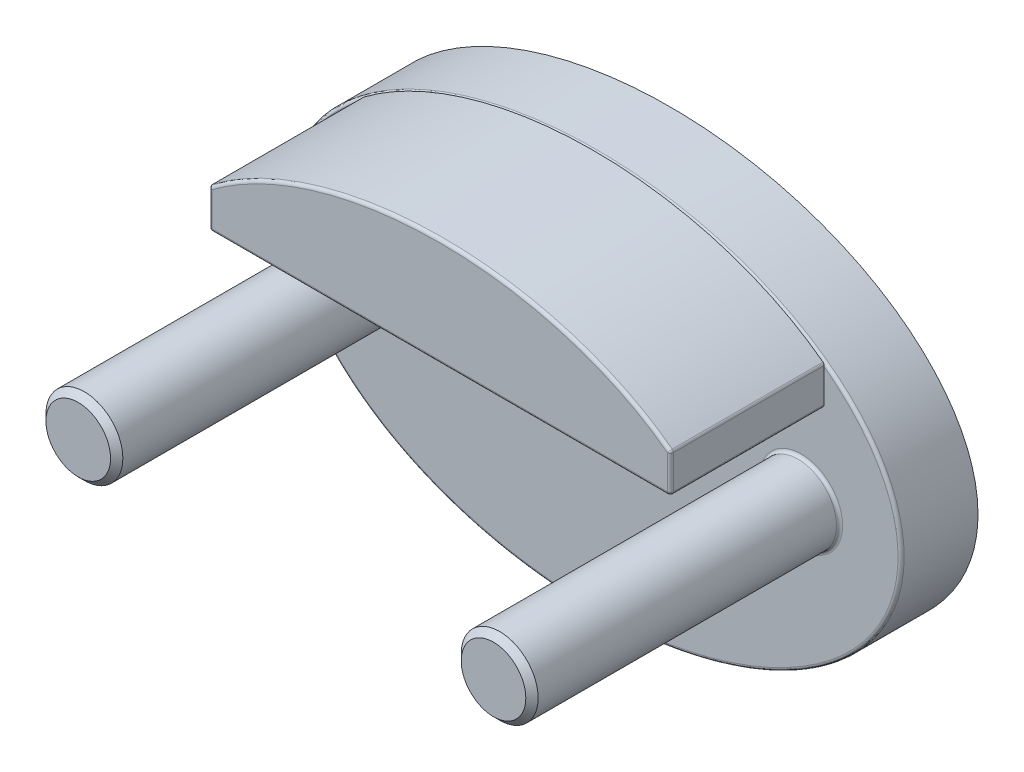
SolidWorks part; units mm, degrees
ref_plane "Face" through (0, 0, 0) normal (0, 0, 1) x (1, 0, 0)
ref_plane "Dessus" through (0, 0, 0) normal (0, 1, 0) x (1, 0, 0)
ref_plane "Droite" through (0, 0, 0) normal (1, 0, 0) x (0, 0, -1)
sketch "Esquisse1" plane through (0, 0, 0) normal (0, 0, 1) x (1, 0, 0)
  ellipse E0 centre (0, 0) end of major axis (20, 0) minor radius 12.9412
  point P1 (0, 0)
  point P7 (0, 0)
  dimension "D1" = 40
extrude "Boss.-Extru.1" add sketch "Esquisse1" along normal blind 5
sketch "Esquisse2" plane through (0, 0, 5) normal (0, 0, 1) x (1, 0, 0)
  circle A0 centre (-13.5, -0.044) radius 2.5
  circle A1 centre (13.5, -0.044) radius 2.5
  point P4 (11, -0.044)
  point P5 (-11, -0.044)
  dimension "D1" = 11
  dimension "D2" = 22
extrude "Boss.-Extru.2" add sketch "Esquisse2" along normal blind 20
chamfer "Chanfrein1" distance 0.4 angle 45 2 edges at (16, -0.044, 25) (-11, -0.044, 25)
fillet "Congé1" radius 0.2 3 edges at (20, 0, 5) (-11, -0.044, 5) (16, -0.044, 5)
sketch "Esquisse4" plane through (0, 0, 5) normal (0, 0, 1) x (1, 0, 0)
  line L0 (0, -12.7412) -> (0, 24.7026) construction
  line L1 (15, 5.9807) -> (-15, 5.9807)
  line L2 (15, 5.9807) -> (15, 8.4807)
  line L4 (-15, 5.9807) -> (-15, 8.4807)
  ellipse E0 centre (0, 0) end of major axis (-19.8, 0) minor radius 12.9923 (15, 8.4807) -> (-15, 8.4807) ccw
  spline S0 degree 3 poles (19.8, -0.5466) (19.8, 0.5466) (19.7454, 1.0862) (19.5858, 1.8857) (19.5191, 2.1517) (19.363, 2.6715) (19.2735, 2.9259) (18.9735, 3.6742) (18.7315, 4.1531) (18.1734, 5.0755) (17.8549, 5.5212) (17.1693, 6.3572) (16.8007, 6.7507) (16.0197, 7.4953) (15.6053, 7.8478) (14.3161, 8.8382) (13.403, 9.4064) (11.9712, 10.1522) (11.4834, 10.3827) (10.4884, 10.8103) (9.9839, 11.0061) (8.4634, 11.5403) (7.4352, 11.8282) (5.354, 12.286) (4.3008, 12.4558) (2.7033, 12.6264) (2.1678, 12.6692) (1.0908, 12.7265) (0.5499, 12.741) (-1.063, 12.7416) (-2.1313, 12.6859) (-4.254, 12.4623) (-5.3084, 12.2945) (-6.8788, 11.9514) (-7.4004, 11.8217) (-8.4395, 11.5294) (-8.9567, 11.3667) (-10.4808, 10.8321) (-11.4671, 10.4127) (-12.8939, 9.6726) (-13.3607, 9.4072) (-14.2742, 8.8339) (-14.7229, 8.5244) (-16.0101, 7.5392) (-16.7959, 6.8064) (-17.8294, 5.5551) (-18.1497, 5.1106) (-18.7129, 4.1877) (-18.9586, 3.7066) (-19.2644, 2.9508) (-19.3559, 2.6927) (-19.5131, 2.1742) (-19.5793, 1.9127) (-19.7403, 1.1216) (-19.7973, 0.5851) (-19.8025, -0.5074) (-19.7504, -1.0496) (-19.5407, -2.122) (-19.3856, -2.6405) (-18.9885, -3.6422) (-18.7452, -4.1281) (-18.1837, -5.0608) (-17.8705, -5.5002) (-17.19, -6.3338) (-16.8227, -6.7281) (-16.0405, -7.4769) (-15.6256, -7.8309) (-14.3441, -8.8191) (-13.4325, -9.3893) (-11.9971, -10.1395) (-11.5055, -10.3725) (-10.5141, -10.7999) (-10.0132, -10.995) (-8.4967, -11.5301) (-7.4672, -11.8201) (-5.8987, -12.1667) (-5.3717, -12.2675) (-4.3099, -12.4401) (-3.7738, -12.5121) (-2.1621, -12.6842) (-1.089, -12.7406) (1.055, -12.7418) (2.1258, -12.6866) (4.2649, -12.4611) (5.3379, -12.2893) (7.4374, -11.828) (8.4682, -11.5387) (10.4875, -10.8291) (11.4762, -10.4094) (13.4012, -9.408) (14.3155, -8.8379) (15.5935, -7.8572) (16.004, -7.5092) (16.7887, -6.7631) (17.1629, -6.3643) (17.848, -5.5303) (18.1617, -5.0929) (18.582, -4.4013) (18.7137, -4.1648) (18.9586, -3.6787) (19.0715, -3.4294) (19.3744, -2.6746) (19.5309, -2.1578) (19.7442, -1.0945) (19.8, -0.5466) (19.8, 0.5466) (19.7454, 1.0862) knots -0.015625 -0.015625 0 0 0.015625 0.015625 0.023437 0.023437 0.03125 0.03125 0.046875 0.046875 0.0625 0.0625 0.078125 0.078125 0.09375 0.09375 0.125 0.125 0.140625 0.140625 0.15625 0.15625 0.1875 0.1875 0.21875 0.21875 0.234375 0.234375 0.25 0.25 0.28125 0.28125 0.3125 0.3125 0.328125 0.328125 0.34375 0.34375 0.375 0.375 0.390625 0.390625 0.40625 0.40625 0.4375 0.4375 0.453125 0.453125 0.46875 0.46875 0.476562 0.476562 0.484375 0.484375 0.5 0.5 0.515625 0.515625 0.53125 0.53125 0.546875 0.546875 0.5625 0.5625 0.578125 0.578125 0.59375 0.59375 0.625 0.625 0.640625 0.640625 0.65625 0.65625 0.6875 0.6875 0.703125 0.703125 0.71875 0.71875 0.75 0.75 0.78125 0.78125 0.8125 0.8125 0.84375 0.84375 0.875 0.875 0.90625 0.90625 0.921875 0.921875 0.9375 0.9375 0.953125 0.953125 0.960937 0.960937 0.96875 0.96875 0.984375 0.984375 1 1 1.015625 1.015625 1.023438 only from (19.8, 0) to (19.8, 0) construction
  point P8 (0, 5.9807)
  dimension "D1" = 30
  dimension "D2" = 2.5
extrude "Boss.-Extru.3" add sketch "Esquisse4" along normal blind 10
fillet "Congé3" radius 0.2 4 edges at (0, 5.9807, 15) (-15, 7.2307, 15) (0, 12.9923, 15) (15, 7.2307, 15)
fillet "Congé4" radius 0.2 8 edges at (14.9635, 8.4626, 14.9152) (14.9414, 6.0393, 14.9414) (-14.9414, 6.0393, 14.9414) (-14.9635, 8.4626, 14.9152) (15, 8.4807, 9.9) (15, 5.9807, 9.9) (-15, 5.9807, 9.9) (-15, 8.4807, 9.9)
